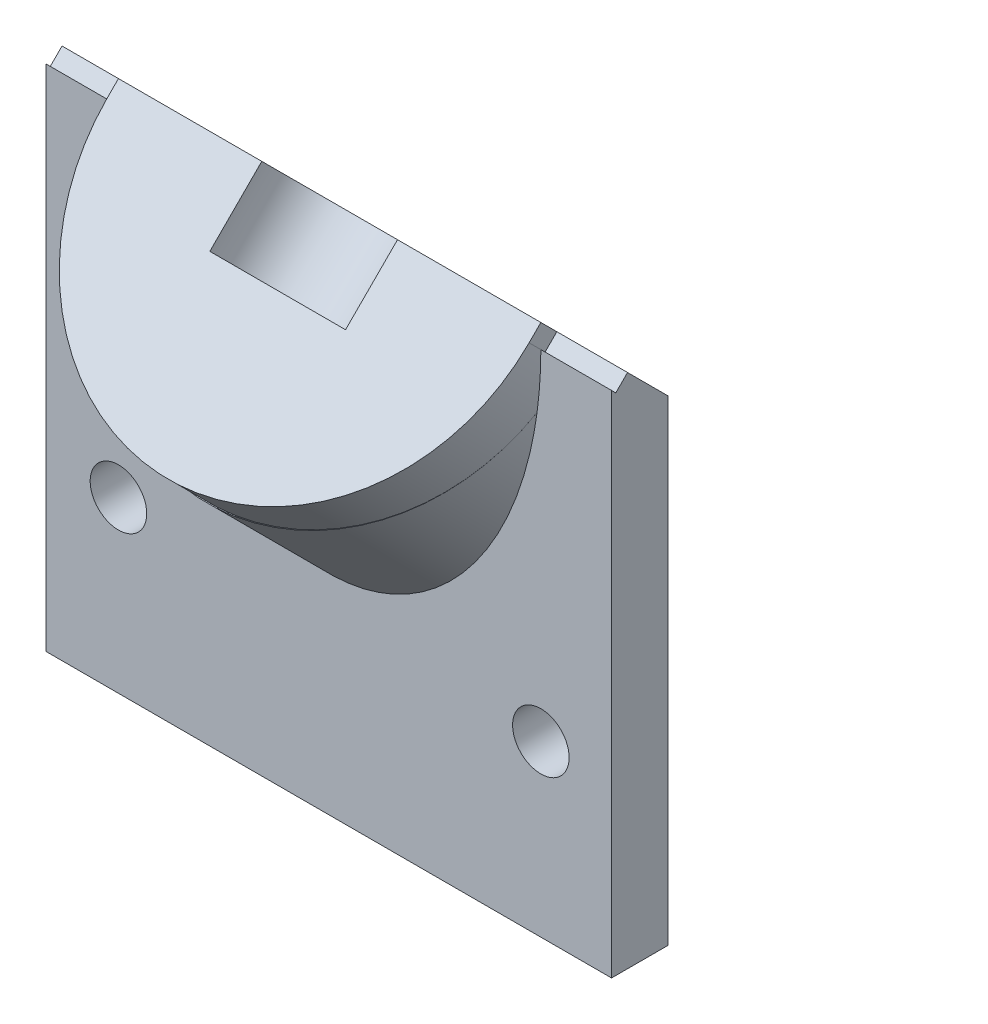
SolidWorks part; units mm, degrees
ref_plane "Front Plane" through (0, 0, 0) normal (0, 0, 1) x (1, 0, 0)
ref_plane "Top Plane" through (0, 0, 0) normal (0, 1, 0) x (1, 0, 0)
ref_plane "Right Plane" through (0, 0, 0) normal (1, 0, 0) x (0, 0, -1)
sketch "Sketch1" plane through (0, 0, 0) normal (0, 0, 1) x (1, 0, 0)
  line L1 (-25, 17.5) -> (25, 17.5)
  line L2 (-25, 17.5) -> (-25, -17.5)
  line L3 (-25, -17.5) -> (25, -17.5)
  line L4 (25, 17.5) -> (25, -17.5)
  line L5 (-25, 17.5) -> (25, -17.5) construction
  line L6 (-25, -17.5) -> (25, 17.5) construction
  point P0 (0, 0)
  dimension "D1" = 50
  dimension "D2" = 35
extrude "Boss-Extrude1" add sketch "Sketch1" along normal blind 5
sketch "Sketch3" plane through (25, 0, 0) normal (1, 0, 0) x (0, 0, -1)
  line L0 (-5, 17.5) -> (0, 17.5)
  line L1 (0, 17.5) -> (0, 22.5)
  line L2 (0, 22.5) -> (-5, 17.5)
extrude "Boss-Extrude2" add sketch "Sketch3" against normal blind 50
sketch "Sketch4" plane through (0, 11.25, 11.25) normal (0, 0.7071, 0.7071) x (1, 0, 0)
  circle A0 centre (0, 12.3744) radius 18.75
extrude "Boss-Extrude3" add sketch "Sketch4" along normal blind 50 and the other way blind 50
sketch "Sketch5" plane through (0, 46.6053, 46.6053) normal (0, 0.7071, 0.7071) x (1, 0, 0)
  line L2 (-18.75, 12.3744) -> (18.75, 12.3744)
  arc A0 (18.75, 12.3744) -> (-18.75, 12.3744) centre (0, 12.3744) ccw
  point P10 (0, 12.3744)
extrude "Cut-Extrude1" cut sketch "Sketch5" against normal blind 100
sketch "Sketch8" plane through (0, -24.1053, -24.1053) normal (0, -0.7071, -0.7071) x (1, 0, 0)
  line L0 (-18.5965, -12.3688) -> (18.75, -12.3744)
  circle A0 centre (16.7612, -4.478) radius 0.2219
  arc A1 (18.7498, -12.3744) -> (-18.5965, -12.3688) centre (0.0766, -12.3688) ccw
sketch "Sketch9" plane through (0, 11.25, 11.25) normal (0, 0.7071, 0.7071) x (1, 0, 0)
  line L0 (-25, 12.3744) -> (25, 12.3744)
  line L1 (-25, 15.9099) -> (-25, 8.8388) construction
  line L2 (25, 15.9099) -> (25, 8.8388) construction
  line L3 (25, 12.3744) -> (25, -31.6949)
  line L4 (25, -31.6949) -> (-25, -31.6949)
  line L5 (-25, -31.6949) -> (-25, 12.3744)
extrude "Cut-Extrude2" cut sketch "Sketch9" along normal blind 100
sketch "Sketch10" plane through (0, 0, 0) normal (0, 0, -1) x (-1, 0, 0)
  line L0 (-25, -17.5) -> (25, -17.5)
  line L1 (25, -17.5) -> (25, 22.5)
  line L2 (25, 22.5) -> (-25, 22.5)
  line L3 (-25, 22.5) -> (-25, -17.5)
extrude "Cut-Extrude3" cut sketch "Sketch10" along normal blind 100
sketch "Sketch11" plane through (0, -17.5, 0) normal (0, 1, 0) x (1, 0, 0)
  line L0 (-18.5031, 30.7107) -> (-17.7623, 6.4808)
  line L1 (-17.7623, 6.4808) -> (17.5528, 7.5605)
  line L2 (17.5528, 7.5605) -> (18.5027, 30.7107)
  line L3 (18.5027, 30.7107) -> (-18.5031, 30.7107)
  ellipse E0 centre (0.0766, 32.8514) end of major axis (18.7498, 32.8514) minor radius 13.2039 (-18.5965, 32.8514) -> (18.7498, 32.8553) ccw construction
extrude "Cut-Extrude4" cut sketch "Sketch11" against normal blind 100
sketch "Sketch12" plane through (25, 0, 0) normal (1, 0, 0) x (0, 0, -1)
  line L0 (-5, 17.5) -> (0, 17.5)
  line L1 (0, -17.5) -> (0, 22.5) construction
  line L2 (0, 17.5) -> (0, 22.5)
  line L3 (0, 22.5) -> (-5, 17.5)
extrude "Boss-Extrude4" add sketch "Sketch12" against normal blind 50
sketch "Sketch13" plane through (25, 0, 0) normal (1, 0, 0) x (0, 0, -1)
  line L0 (0, 22.5) -> (-5, 17.5) construction
  line L2 (-5, 17.5) -> (-5, -4.0165) construction
  line L3 (0, 17.5) -> (0, 12.5)
  line L4 (0, -17.5) -> (0, 22.5) construction
  line L5 (0, 12.5) -> (-5, 17.5)
  line L6 (0, 22.5) -> (0, 17.5)
  line L7 (-5, 17.5) -> (0, 22.5)
extrude "Cut-Extrude5" cut sketch "Sketch13" against normal blind 50
sketch "Sketch14" plane through (25, 0, 0) normal (1, 0, 0) x (0, 0, -1)
  line L0 (-5, -17.5) -> (0, -17.5)
  line L1 (0, -17.5) -> (0, -22.5)
  line L2 (0, -22.5) -> (-5, -22.5)
  line L3 (-5, -22.5) -> (-5, -17.5)
  dimension "D1" = 5
extrude "Boss-Extrude5" add sketch "Sketch14" against normal blind 50
sketch "Sketch15" plane through (0, 11.25, 11.25) normal (0, 0.7071, 0.7071) x (1, 0, 0)
  line L0 (-18.5965, 12.3688) -> (18.75, 12.3744)
  arc A0 (-18.5965, 12.3688) -> (18.7498, 12.3744) centre (0.0766, 12.3716) ccw
  line M1 (18.4136, 8.8388) -> (-18.4136, 8.8388)
extrude "Boss-Extrude6" add sketch "Sketch15" along normal blind 5 contours A0 L0 M1 | A0 M1 region at (0.0816, 18.7528, 3.7472) region at (0.0766, 13.0219, 9.4781)
sketch "Sketch16" plane through (-25, 0, 0) normal (-1, 0, 0) x (0, 0, 1)
  line L0 (0, 12.5) -> (5, 12.5)
  line L1 (5, 17.5) -> (5, -22.5) construction
  line L2 (5, 12.5) -> (5, 22.4922)
  line L3 (6.0395, 23.5316) -> (2.5039, 19.9961) construction
  line L4 (5, 22.4922) -> (6.0395, 23.5316)
  line L5 (0, 12.5) -> (0, 23.5316)
  line L7 (6.0395, 23.5316) -> (0, 29.5711)
  line L8 (0, 29.5711) -> (0, 23.5316)
extrude "Boss-Extrude7" add sketch "Sketch16" against normal blind 50
sketch "Sketch18" plane through (25, 0, 0) normal (1, 0, 0) x (0, 0, -1)
  line L0 (-5, 22.4922) -> (-6.0395, 23.5316)
  line L1 (-5, 22.4922) -> (-5, 24.5711)
  line L2 (-6.0395, 23.5316) -> (0, 29.5711) construction
  line L3 (-5, 24.5711) -> (-6.0395, 23.5316)
extrude "Cut-Extrude7" cut sketch "Sketch18" against normal blind 50
sketch "Sketch19" plane through (25, 0, 0) normal (1, 0, 0) x (0, 0, -1)
  line L1 (0, -22.5) -> (0, 29.5711) construction
  line L2 (0, 24.5711) -> (0, 19.5711)
  line L3 (0, 19.5711) -> (-5, 24.5711)
  line L4 (-5, 24.5711) -> (0, 29.5711)
  line L5 (0, 29.5711) -> (0, 24.5711)
  line L6 (-5, 24.5711) -> (0, 29.5711)
  line M1 (0, 29.5711) -> (-5, 24.5711)
  line M4 (0, -22.5) -> (0, 29.5711)
extrude "Cut-Extrude8" cut sketch "Sketch19" against normal blind 50 contours L3 M4 M1 region at (25, 24.5711, 1.6667)
sketch "Sketch20" plane through (25, 0, 0) normal (1, 0, 0) x (0, 0, -1)
  line L0 (-5, 22.4922) -> (-6.0395, 23.5316)
  line L1 (-6.0395, 23.5316) -> (-5, 24.5711)
  line L2 (-5, 24.5711) -> (-5, 22.4922)
extrude "Boss-Extrude8" add sketch "Sketch20" against normal blind 50
sketch "Sketch21" plane through (0, 14.7855, 14.7855) normal (0, 0.7071, 0.7071) x (1, 0, 0)
  line L0 (-25, 13.8388) -> (25, 13.8388) construction
  line L1 (18.7498, 12.3688) -> (25, 12.3688)
  line L2 (18.7498, 12.3688) -> (18.7498, 13.8388)
  line L3 (18.7498, 13.8388) -> (25, 13.8388)
  line L4 (25, 12.3688) -> (25, 13.8388)
  line L5 (-25, 12.3688) -> (-18.5967, 12.3688)
  line L6 (-25, 12.3688) -> (-25, 13.8388)
  line L7 (-25, 13.8388) -> (-18.5967, 13.8388)
  line L8 (-18.5967, 12.3688) -> (-18.5967, 13.8388)
extrude "Cut-Extrude9" cut sketch "Sketch21" against normal blind 2
sketch "Sketch22" plane through (0, 9.7855, -9.7855) normal (0, 0.7071, -0.7071) x (1, 0, 0)
  line L0 (-18.5967, -20.9099) -> (18.7498, -20.9099) construction
  circle A0 centre (0.0765, -20.9099) radius 6
  dimension "D1" = 12
extrude "Cut-Extrude10" cut sketch "Sketch22" against normal blind 6.5 contours A0
sketch "Sketch23" plane through (0, 0, 5) normal (0, 0, 1) x (1, 0, 0)
  line L0 (-18.5967, 22.4922) -> (-18.5967, -22.5) construction
  line L1 (-25, -22.5) -> (25, -22.5) construction
  line L2 (-25, -7.5) -> (-18.5967, -7.5) construction
  line L3 (-25, 22.4922) -> (-25, -22.5) construction
  line L4 (18.7498, 22.4922) -> (18.7498, -22.5) construction
  circle A0 centre (-18.5967, -7.5) radius 2.5
  circle A1 centre (18.7498, -7.5) radius 2.5
  dimension "D1" = 15
extrude "Cut-Extrude11" cut sketch "Sketch23" against normal blind 6.5 contours A0 | A1
